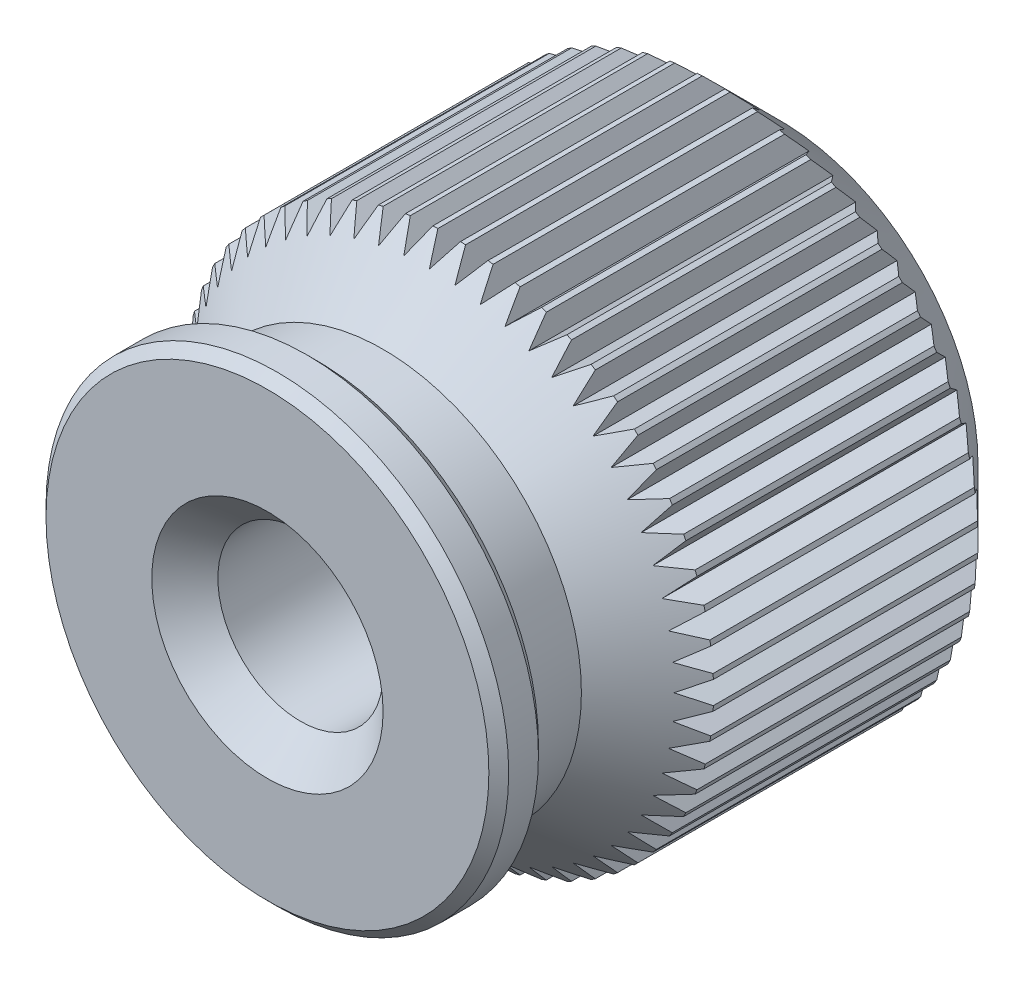
SolidWorks part; units mm, degrees
ref_plane "Спереди" through (0, 0, 0) normal (0, 0, 1) x (1, 0, 0)
ref_plane "Сверху" through (0, 0, 0) normal (0, 1, 0) x (1, 0, 0)
ref_plane "Справа" through (0, 0, 0) normal (1, 0, 0) x (0, 0, -1)
sketch "Эскиз1" plane through (0, 0, 0) normal (0, 0, 1) x (1, 0, 0)
  circle A0 centre (0, 0) radius 8
  dimension "D1" = 16
extrude "Вытянуть1" add sketch "Эскиз1" along normal blind 12
sketch "Эскиз2" plane through (0, 0, 12) normal (0, 0, 1) x (1, 0, 0)
  circle A0 centre (0, 0) radius 6
  dimension "D1" = 12
extrude "Вытянуть2" add sketch "Эскиз2" along normal blind 2
sketch "Эскиз3" plane through (0, 0, 14) normal (0, 0, 1) x (1, 0, 0)
  circle A0 centre (0, 0) radius 2.5
  dimension "D1" = 5
extrude "Вырез-Вытянуть1" cut sketch "Эскиз3" against normal blind 14
chamfer "Фаска1" distance 1 angle 45
chamfer "Фаска2" distance 2 angle 45
sketch "Эскиз4" plane through (0, 0, 14) normal (0, 0, 1) x (1, 0, 0)
  circle A0 centre (0, 0) radius 7
  circle A2 centre (0, 0) radius 2.5 construction
  circle A3 centre (0, 0) radius 2.5
  dimension "D1" = 14
extrude "Вытянуть3" add sketch "Эскиз4" along normal blind 1.5
chamfer "Фаска3" distance 1 angle 45
chamfer "Фаска4" distance 0.3 angle 45
sketch "Эскиз5" plane through (0, 0, 15.5) normal (0, 0, 1) x (1, 0, 0)
  line L0 (0, 0) -> (0, 9.7593) construction
  line L1 (0, 7.4) -> (-0.6888, 8.5931)
  line L2 (-0.6888, 8.5931) -> (0.6888, 8.5931)
  line L3 (0.6888, 8.5931) -> (0, 7.4)
  circle A0 centre (0, 0) radius 8 construction
  dimension "D1" = 60
  dimension "D2" = 0.6
extrude "Вырез-Вытянуть2" cut sketch "Эскиз5" against normal blind 20
pattern_circular "Круговой массив1" count 60 over 360
